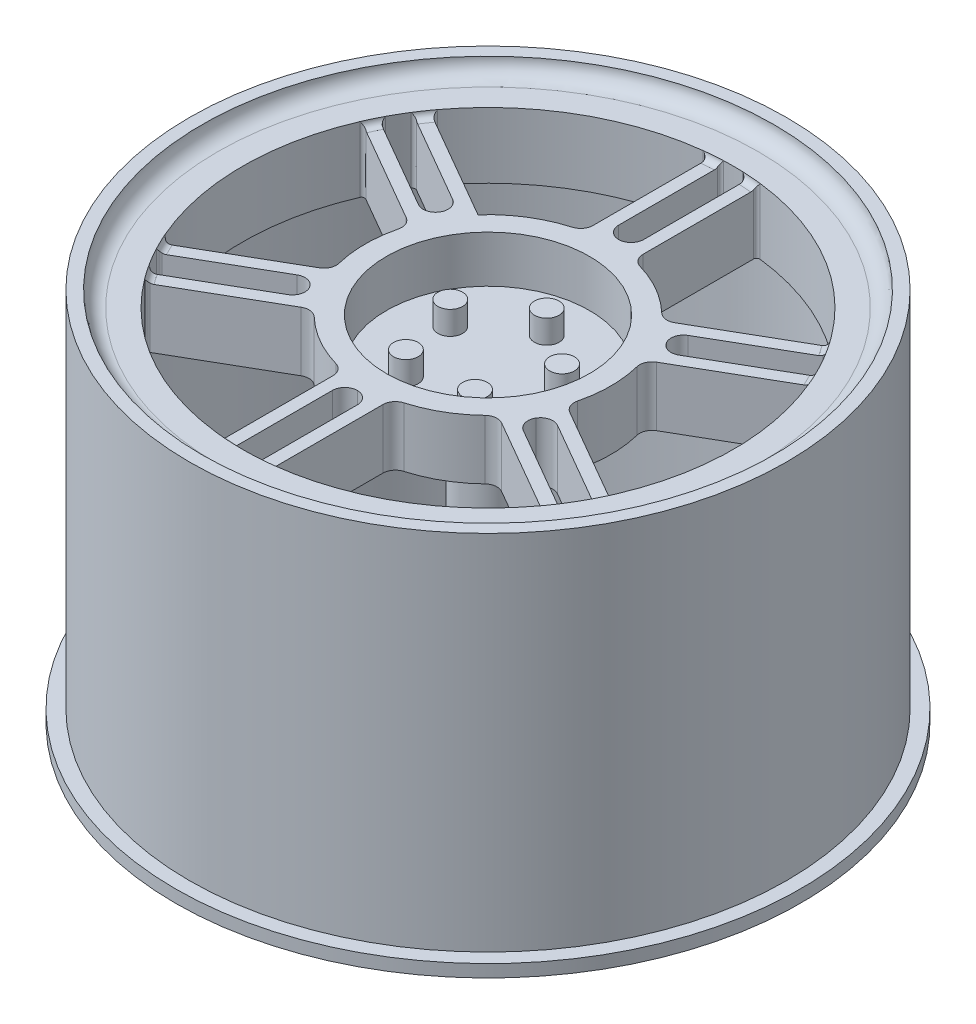
SolidWorks part; units mm, degrees
material "AISI 1035 Steel (SS)"
ref_plane "Front Plane" through (0, 0, 0) normal (0, 0, 1) x (1, 0, 0)
ref_plane "Top Plane" through (0, 0, 0) normal (0, 1, 0) x (1, 0, 0)
ref_plane "Right Plane" through (0, 0, 0) normal (1, 0, 0) x (0, 0, -1)
sketch "Sketch1" plane through (0, 0, 0) normal (0, 1, 0) x (1, 0, 0)
  circle A0 centre (0, 0) radius 10
  dimension "D1" = 20
extrude "Inner Lip" add sketch "Sketch1" along normal blind 0.4
sketch "Sketch2" plane through (0, 0.4, 0) normal (0, 1, 0) x (1, 0, 0)
  circle A0 centre (0, 0) radius 9.55
  dimension "D1" = 19.1
extrude "Boss-Extrude2" add sketch "Sketch2" along normal blind 11.6
sketch "Sketch3" plane through (0, 0, 0) normal (0, -1, 0) x (1, 0, 0)
  circle A0 centre (0, 0) radius 8.5
  dimension "D1" = 17
extrude "Cut-Extrude1" cut sketch "Sketch3" against normal blind 9.4
sketch "Sketch4" plane through (0, 12, 0) normal (0, 1, 0) x (1, 0, 0)
  circle A2 centre (0, 0) radius 9.15
  circle A3 centre (0, 0) radius 9.15
  dimension "D1" = 0.4
extrude "Cut-Extrude2" cut sketch "Sketch4" against normal blind 0.5
sketch "Sketch5" plane through (0, 12, 0) normal (0, 1, 0) x (1, 0, 0)
  circle A2 centre (0, 0) radius 7.85
  circle A3 centre (0, 0) radius 7.85
  dimension "D1" = 1.7
extrude "Cut-Extrude3" cut sketch "Sketch5" against normal blind 2.2
sketch "Sketch6" plane through (0, 9.8, 0) normal (0, 1, 0) x (1, 0, 0)
  circle A0 centre (0, 0) radius 3.25
  dimension "D1" = 6.5
sketch "Sketch7" plane through (0, 9.8, 0) normal (0, 1, 0) x (1, 0, 0)
  line L0 (0, 0) -> (0, 11.6349) construction
  line L1 (0.7972, 7.8094) -> (0.7972, 3.722)
  line L3 (-0.8, 3.722) -> (-0.8, 7.8091)
  line L4 (0.4, 7.8398) -> (0.4, 4.1802)
  line L5 (0.4, 4.1802) -> (-0.4, 4.1802)
  line L6 (-0.4, 4.1802) -> (-0.4, 7.8398)
  circle A0 centre (0, 0) radius 7.85 construction
  circle A1 centre (0, 0) radius 7.85 construction
  arc A2 (0.7972, 7.8094) -> (0.4, 7.8398) centre (0, 0) ccw
  arc A3 (-0.4, 7.8398) -> (-0.8, 7.8091) centre (0, 0) ccw
  arc A4 (-0.8, 3.722) -> (0, 3.807) centre (0, 0) cw
  arc A5 (0.7972, 3.722) -> (0, 3.8064) centre (0, 0) ccw
  point P15 (0, 4.1802)
  circle M13 centre (0, 0) radius 7.85
  dimension "D3" = 0.8
  dimension "D4" = 3.8064
  dimension "D5" = 3.807
  dimension "D1" = 0.7972
  dimension "D2" = 0.8
  dimension "D6" = 4.1802
extrude "Boss-Extrude3" add sketch "Sketch7" along normal blind 1.5 contours A4 L0 L5 L6 L3 M13 | L0 A5 L1 L4 L5 M13 region at (0.5647, 9.8, -5.6365) region at (-0.5662, 9.8, -5.6378)
pattern_circular "CirPattern1" count 6 over 360 about axis through (0, 11.5, 0) along (0, 1, 0) of "Boss-Extrude3"
sketch "Sketch8" plane through (0, 9.8, 0) normal (0, 1, 0) x (1, 0, 0)
  circle A0 centre (0, 0) radius 3.9321
extrude "Boss-Extrude4" add sketch "Sketch8" along normal blind 1.5
extrude "Cut-Extrude4" cut sketch "Sketch6" along normal blind 1.5 contours A0
sketch "Sketch9" plane through (0, 9.8, 0) normal (0, 1, 0) x (1, 0, 0)
  line L0 (7.1617, 3.2143) -> (3.7332, 1.2348) construction
  line L1 (3.7341, -1.2321) -> (7.1629, -3.2117) construction
  line L2 (6.3646, -4.5951) -> (2.936, -2.6156) construction
  line L3 (0.8, -3.8499) -> (0.8, -7.8091) construction
  line L4 (-0.7972, -7.8094) -> (-0.7972, -3.8504) construction
  line L5 (-2.9341, -2.6178) -> (-6.3629, -4.5974) construction
  line L6 (-7.1617, -3.2143) -> (-3.7332, -1.2348) construction
  line L7 (-3.7341, 1.2321) -> (-7.1629, 3.2117) construction
  line L8 (-6.3646, 4.5951) -> (-2.936, 2.6156) construction
  line L9 (-0.8, 3.8499) -> (-0.8, 7.8091) construction
  line L10 (0.7972, 7.8094) -> (0.7972, 3.8504) construction
  line L11 (2.9341, 2.6178) -> (6.3629, 4.5974) construction
  line L12 (7.1617, 3.2143) -> (3.7332, 1.2348)
  line L13 (3.7341, -1.2321) -> (7.1629, -3.2117)
  line L14 (6.3646, -4.5951) -> (2.936, -2.6156)
  line L15 (0.8, -3.8499) -> (0.8, -7.8091)
  line L16 (-0.7972, -7.8094) -> (-0.7972, -3.8504)
  line L17 (-2.9341, -2.6178) -> (-6.3629, -4.5974)
  line L18 (-7.1617, -3.2143) -> (-3.7332, -1.2348)
  line L19 (-3.7341, 1.2321) -> (-7.1629, 3.2117)
  line L20 (-6.3646, 4.5951) -> (-2.936, 2.6156)
  line L21 (-0.8, 3.8499) -> (-0.8, 7.8091)
  line L22 (0.7972, 7.8094) -> (0.7972, 3.8504)
  line L23 (2.9341, 2.6178) -> (6.3629, 4.5974)
  line L24 (-3.4202, -2.4365) -> (-3.8202, -1.7437) construction
  line L25 (-3.8202, -1.7437) -> (-6.9895, -3.5735) construction
  line L26 (-6.5895, -4.2663) -> (-3.4202, -2.4365) construction
  line L27 (-3.8202, 1.7437) -> (-3.4202, 2.4365) construction
  line L28 (-3.4202, 2.4365) -> (-6.5895, 4.2663) construction
  line L29 (-6.9895, 3.5735) -> (-3.8202, 1.7437) construction
  line L30 (0.4, -4.1802) -> (-0.4, -4.1802) construction
  line L31 (-0.4, -4.1802) -> (-0.4, -7.8398) construction
  line L32 (0.4, -7.8398) -> (0.4, -4.1802) construction
  line L33 (3.8202, -1.7437) -> (3.4202, -2.4365) construction
  line L34 (3.4202, -2.4365) -> (6.5895, -4.2663) construction
  line L35 (6.9895, -3.5735) -> (3.8202, -1.7437) construction
  line L36 (3.4202, 2.4365) -> (3.8202, 1.7437) construction
  line L37 (3.8202, 1.7437) -> (6.9895, 3.5735) construction
  line L38 (6.5895, 4.2663) -> (3.4202, 2.4365) construction
  line L39 (-0.4, 4.1802) -> (0.4, 4.1802) construction
  line L40 (0.4, 4.1802) -> (0.4, 7.8398) construction
  line L41 (-0.4, 7.8398) -> (-0.4, 4.1802) construction
  line L42 (-3.4202, -2.4365) -> (-3.8202, -1.7437)
  line L43 (-3.8202, -1.7437) -> (-6.9895, -3.5735)
  line L44 (-6.5895, -4.2663) -> (-3.4202, -2.4365)
  line L45 (-3.8202, 1.7437) -> (-3.4202, 2.4365)
  line L46 (-3.4202, 2.4365) -> (-6.5895, 4.2663)
  line L47 (-6.9895, 3.5735) -> (-3.8202, 1.7437)
  line L48 (0.4, -4.1802) -> (-0.4, -4.1802)
  line L49 (-0.4, -4.1802) -> (-0.4, -7.8398)
  line L50 (0.4, -7.8398) -> (0.4, -4.1802)
  line L51 (3.8202, -1.7437) -> (3.4202, -2.4365)
  line L52 (3.4202, -2.4365) -> (6.5895, -4.2663)
  line L53 (6.9895, -3.5735) -> (3.8202, -1.7437)
  line L54 (3.4202, 2.4365) -> (3.8202, 1.7437)
  line L55 (3.8202, 1.7437) -> (6.9895, 3.5735)
  line L56 (6.5895, 4.2663) -> (3.4202, 2.4365)
  line L57 (-0.4, 4.1802) -> (0.4, 4.1802)
  line L58 (0.4, 4.1802) -> (0.4, 7.8398)
  line L59 (-0.4, 7.8398) -> (-0.4, 4.1802)
  arc A0 (3.7341, -1.2321) -> (3.7332, 1.2348) centre (0, 0) ccw construction
  arc A1 (7.1629, -3.2117) -> (7.1617, 3.2143) centre (0, 0) ccw construction
  arc A2 (0.8, -3.8499) -> (2.936, -2.6156) centre (0, 0) ccw construction
  arc A3 (0.8, -7.8091) -> (6.3646, -4.5951) centre (0, 0) ccw construction
  arc A4 (-2.9341, -2.6178) -> (-0.7972, -3.8504) centre (0, 0) ccw construction
  arc A5 (-6.3629, -4.5974) -> (-0.7972, -7.8094) centre (0, 0) ccw construction
  arc A6 (-3.7341, 1.2321) -> (-3.7332, -1.2348) centre (0, 0) ccw construction
  arc A7 (-7.1629, 3.2117) -> (-7.1617, -3.2143) centre (0, 0) ccw construction
  arc A8 (-0.8, 3.8499) -> (-2.936, 2.6156) centre (0, 0) ccw construction
  arc A9 (-0.8, 7.8091) -> (-6.3646, 4.5951) centre (0, 0) ccw construction
  arc A10 (2.9341, 2.6178) -> (0.7972, 3.8504) centre (0, 0) ccw construction
  arc A11 (6.3629, 4.5974) -> (0.7972, 7.8094) centre (0, 0) ccw construction
  arc A12 (3.7341, -1.2321) -> (3.7332, 1.2348) centre (0, 0) ccw
  arc A13 (7.1629, -3.2117) -> (7.1617, 3.2143) centre (0, 0) ccw
  arc A14 (0.8, -3.8499) -> (2.936, -2.6156) centre (0, 0) ccw
  arc A15 (0.8, -7.8091) -> (6.3646, -4.5951) centre (0, 0) ccw
  arc A16 (-2.9341, -2.6178) -> (-0.7972, -3.8504) centre (0, 0) ccw
  arc A17 (-6.3629, -4.5974) -> (-0.7972, -7.8094) centre (0, 0) ccw
  arc A18 (-3.7341, 1.2321) -> (-3.7332, -1.2348) centre (0, 0) ccw
  arc A19 (-7.1629, 3.2117) -> (-7.1617, -3.2143) centre (0, 0) ccw
  arc A20 (-0.8, 3.8499) -> (-2.936, 2.6156) centre (0, 0) ccw
  arc A21 (-0.8, 7.8091) -> (-6.3646, 4.5951) centre (0, 0) ccw
  arc A22 (2.9341, 2.6178) -> (0.7972, 3.8504) centre (0, 0) ccw
  arc A23 (6.3629, 4.5974) -> (0.7972, 7.8094) centre (0, 0) ccw
  arc A24 (-6.9895, -3.5735) -> (-6.5895, -4.2663) centre (0, 0) ccw construction
  arc A25 (-6.5895, 4.2663) -> (-6.9895, 3.5735) centre (0, 0) ccw construction
  arc A26 (-0.4, -7.8398) -> (0.4, -7.8398) centre (0, 0) ccw construction
  arc A27 (6.5895, -4.2663) -> (6.9895, -3.5735) centre (0, 0) ccw construction
  arc A28 (6.9895, 3.5735) -> (6.5895, 4.2663) centre (0, 0) ccw construction
  arc A29 (0.4, 7.8398) -> (-0.4, 7.8398) centre (0, 0) ccw construction
  arc A30 (-6.9895, -3.5735) -> (-6.5895, -4.2663) centre (0, 0) ccw
  arc A31 (-6.5895, 4.2663) -> (-6.9895, 3.5735) centre (0, 0) ccw
  arc A32 (-0.4, -7.8398) -> (0.4, -7.8398) centre (0, 0) ccw
  arc A33 (6.5895, -4.2663) -> (6.9895, -3.5735) centre (0, 0) ccw
  arc A34 (6.9895, 3.5735) -> (6.5895, 4.2663) centre (0, 0) ccw
  arc A35 (0.4, 7.8398) -> (-0.4, 7.8398) centre (0, 0) ccw
extrude "Cut-Extrude5" cut sketch "Sketch9" against normal blind 1.5
sketch "Sketch10" plane through (0, 9.8, 0) normal (0, 1, 0) x (1, 0, 0)
  circle A0 centre (0, 1.8805) radius 0.3946
extrude "Boss-Extrude5" add sketch "Sketch10" along normal blind 0.75
pattern_circular "CirPattern2" count 5 over 360 about axis through (0, 11.3, 0) along (0, 1, 0) of "Boss-Extrude5"
sketch "Sketch11" plane through (0, 9.4, 0) normal (0, -1, 0) x (1, 0, 0)
  circle A0 centre (0, 0) radius 2.75
  dimension "D1" = 5.5
ref_plane "Plane1" through (0, 8.4, 0) normal (0, -1, 0) x (-1, 0, 0)
sketch "Sketch12" plane through (0, 8.4, 0) normal (0, -1, 0) x (-1, 0, 0)
  circle A0 centre (0, 0) radius 1.951
loft "Loft1" add profiles "Sketch12", "Sketch11" connector at (1.7632, 8.4, -0.8351) connector at (-2.5309, 9.4, -1.0757)
sketch "Sketch13" plane through (0, 8.4, 0) normal (0, -1, 0) x (1, 0, 0)
  circle A0 centre (0, 0) radius 0.95
  dimension "D1" = 1.9
extrude "Boss-Extrude6" add sketch "Sketch13" along normal blind 7
dome "Dome1" faces to dome 1 distance 0.8 reverse direction no elliptical dome no face at (0, 1.4, -0.95) parameters "D1"=0.8
fillet "Fillet1" radius 0.5 1 edges at (0, 11.5, 9.15)
fillet "Fillet3" radius 0.4 23 edges at (3.7332, 10.35, -1.2348) (3.7341, 10.35, 1.2321) (3.8202, 10.35, 1.7437) (3.4202, 10.35, 2.4365) (2.936, 10.35, 2.6156) (0.8, 10.35, 3.8499) (-0.7972, 10.35, 3.8504) (-2.9341, 10.35, 2.6178) (-3.7332, 10.35, 1.2348) (-3.7341, 10.35, -1.2321) (-0.8, 10.35, -3.8499) (0.7972, 10.35, -3.8504) (2.9341, 10.35, -2.6178) (3.8202, 10.35, -1.7437) (3.4202, 10.35, -2.4365) (0.4, 10.35, -4.1802) (-0.4, 10.35, -4.1802) (-3.4202, 10.35, -2.4365) (-3.8202, 10.35, -1.7437) (-3.4202, 10.35, 2.4365) (-3.8202, 10.35, 1.7437) (0.4, 10.35, 4.1802) (-0.4, 10.35, 4.1802)
fillet "Fillet4" radius 0.1 24 edges at (6.5895, 10.35, 4.2663) (6.9895, 10.35, 3.5735) (6.3646, 10.35, 4.5951) (7.1629, 10.35, 3.2117) (6.9895, 10.35, -3.5735) (7.1617, 10.35, -3.2143) (6.5895, 10.35, -4.2663) (6.3629, 10.35, -4.5974) (0.4, 10.35, -7.8398) (0.7972, 10.35, -7.8094) (-0.4, 10.35, -7.8398) (-0.8, 10.35, -7.8091) (-6.5895, 10.35, -4.2663) (-6.3646, 10.35, -4.5951) (-6.9895, 10.35, -3.5735) (-7.1629, 10.35, -3.2117) (-6.9895, 10.35, 3.5735) (-6.5895, 10.35, 4.2663) (-6.3629, 10.35, 4.5974) (-7.1617, 10.35, 3.2143) (0.8, 10.35, 7.8091) (0.4, 10.35, 7.8398) (-0.4, 10.35, 7.8398) (-0.7972, 10.35, 7.8094)
fillet "Fillet5" radius 0.2 12 edges at (-0.6082, 11.3, -7.8264) (0.6068, 11.3, -7.8265) (-7.082, 11.3, -3.3865) (-6.4746, 11.3, -4.4387) (-6.4738, 11.3, 4.4399) (-7.0813, 11.3, 3.3878) (0.6082, 11.3, 7.8264) (-0.6068, 11.3, 7.8265) (7.082, 11.3, 3.3865) (6.4746, 11.3, 4.4387) (6.4738, 11.3, -4.4399) (7.0813, 11.3, -3.3878)
